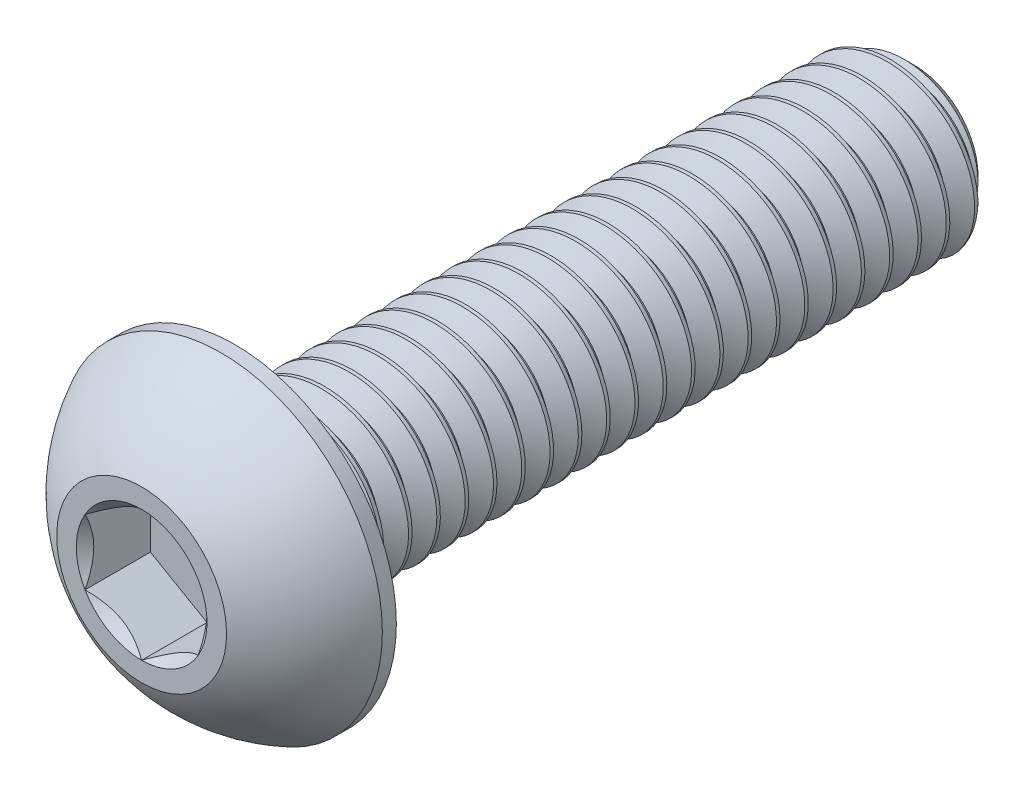
SolidWorks part; units mm, degrees
ref_plane "Front" through (0, 0, 0) normal (0, 0, 1) x (1, 0, 0)
ref_plane "Top" through (0, 0, 0) normal (0, 1, 0) x (1, 0, 0)
ref_plane "Right" through (0, 0, 0) normal (1, 0, 0) x (0, 0, -1)
sketch "Sketch1" plane through (0, 0, 0) normal (1, 0, 0) x (0, 0, -1)
  line L2 (1.65, 1.5) -> (13.65, 1.5)
  line L3 (13.65, 1.5) -> (13.65, 0)
  line L4 (13.65, 0) -> (1.65, 0)
  line L6 (1.4025, 2.85) -> (1.65, 2.85) construction
  line L7 (13.65, 1.5) -> (13.65, -1.5) construction
  line L8 (0, 0) -> (1.65, 0) construction
  line L9 (1.65, 2.85) -> (1.65, -2.85) construction
  line L11 (1.65, 1.5) -> (1.65, 0)
  line L13 (0, 1) -> (0, -1) construction
  line L14 (0, 1) -> (0, 1.5) construction
  arc A3 (0, 1.5) -> (1.4025, 2.85) centre (2.7948, 0) cw construction
  dimension "D1" = 0.2475
  dimension "Head Ht" = 1.65
  dimension "Head Dia" = 5.7
  dimension "Dia" = 3
  dimension "Lg" = 12
  dimension "Hex" = 2
revolve "Revolve1" add sketch "Sketch1" angle 360 about L4
sketch "Sketch3" plane through (0, 0, -13.65) normal (0, 0, -1) x (-1, 0, 0)
  circle A0 centre (0, 0) radius 1.5
curve "Helix/Spiral1" pitch 0.5 height 12.5 radius 1.5 centre (0, 0, -13.65) axis (0, 0, 1) start towards (0, 1, 0)
sketch "Sketch2" plane through (0, 0, 0) normal (1, 0, 0) x (0, 0, -1)
  line L0 (13.65, 1.5) -> (14.0875, 1.5)
  line L1 (14.0875, 1.5) -> (13.9, 1.1752)
  line L2 (13.9, 1.1752) -> (13.8375, 1.1752)
  line L3 (13.8375, 1.1752) -> (13.65, 1.5)
  line L4 (13.7438, 1.3376) -> (13.9938, 1.3376) construction
  dimension "D1" = 60
  dimension "D2" = 0.0625
  dimension "D3" = 0.25
chamfer "Chamfer1" distance 0.375 angle 45 1 edges at (0, 1.5, -13.65)
sweep "Cut-Sweep1" cut profiles "Sketch2" path "Helix/Spiral1"
sketch "Sketch7" plane through (0, 0, 0) normal (1, 0, 0) x (0, 0, -1)
  line L6 (1.4025, 2.85) -> (1.65, 2.85) construction
  line L8 (0, 0) -> (1.65, 0) construction
  line L11 (1.65, 2.85) -> (1.65, -2.85) construction
  line L12 (1.4025, 2.85) -> (1.65, 2.85)
  line L13 (0, 0) -> (1.65, 0)
  line L14 (0, 1) -> (0, -1) construction
  line L15 (1.65, 2.85) -> (1.65, 0)
  line L16 (0, 1.5) -> (0, 0)
  arc A2 (1.4025, 2.85) -> (0, 1.5) centre (2.7948, 0) ccw construction
  arc A3 (1.4025, 2.85) -> (0, 1.5) centre (2.7948, 0) ccw
revolve "Revolve2" add sketch "Sketch7" angle 360 about L13
sketch "Sketch5" plane through (0, 0, 0) normal (0, 0, 1) x (1, 0, 0)
  line L1 (1, -0.5774) -> (1, 0.5774)
  line L2 (1, 0.5774) -> (0, 1.1547)
  line L3 (0, 1.1547) -> (-1, 0.5774)
  line L4 (-1, 0.5774) -> (-1, -0.5774)
  line L5 (-1, -0.5774) -> (0, -1.1547)
  line L6 (0, -1.1547) -> (1, -0.5774)
  circle A0 centre (0, 0) radius 1 construction
extrude "Cut-Extrude2" cut sketch "Sketch5" against normal blind 1.155
sketch "Sketch6" plane through (0, 0, 0) normal (0, 0, 1) x (1, 0, 0)
  circle A0 centre (0, 0) radius 1.1547
extrude "Cut-Extrude3" cut sketch "Sketch6" against normal blind 1.155 draft 45
sketch "Sketch9" [suppressed] plane through (0, 0, -4.2164) normal (0, 0, 1) x (1, 0, 0)
  circle A2 centre (0, 0) radius 3.9687
extrude "Boss-Extrude2" [suppressed] add sketch "Sketch9" against normal offset from surface (9.525 mm away) 28.575 up to face at (0, 1.125, -13.65)
sketch "Sketch10" plane through (0, 0, 0) normal (1, 0, 0) x (0, 0, -1)
  line L0 (13.65, 1.5) -> (13.65, -1.5) construction
  point P0 (12.9, -1.5)
  dimension "D1" = 0.75
equation "\"D3@Helix/Spiral1\" = \"Lg@Sketch1\" + \"D4@Helix/Spiral1\""
equation "\"D2@Sketch2\" = \"D4@Helix/Spiral1\" * .125"
equation "\"D3@Sketch2\" = \"D4@Helix/Spiral1\" * .5"
equation "\"D1@Chamfer1\" = \"D4@Helix/Spiral1\" * .75"
equation "\"D1@Cut-Extrude2\" = \"Head Ht@Sketch1\" * .7"
equation "\"D1@Sketch1\" = \"Head Ht@Sketch1\" * .15"
equation "\"D1@Sketch10\" = \"D4@Helix/Spiral1\" * 1.5"
equation "\"D1@Cut-Extrude3\" = \"D1@Cut-Extrude2\""
